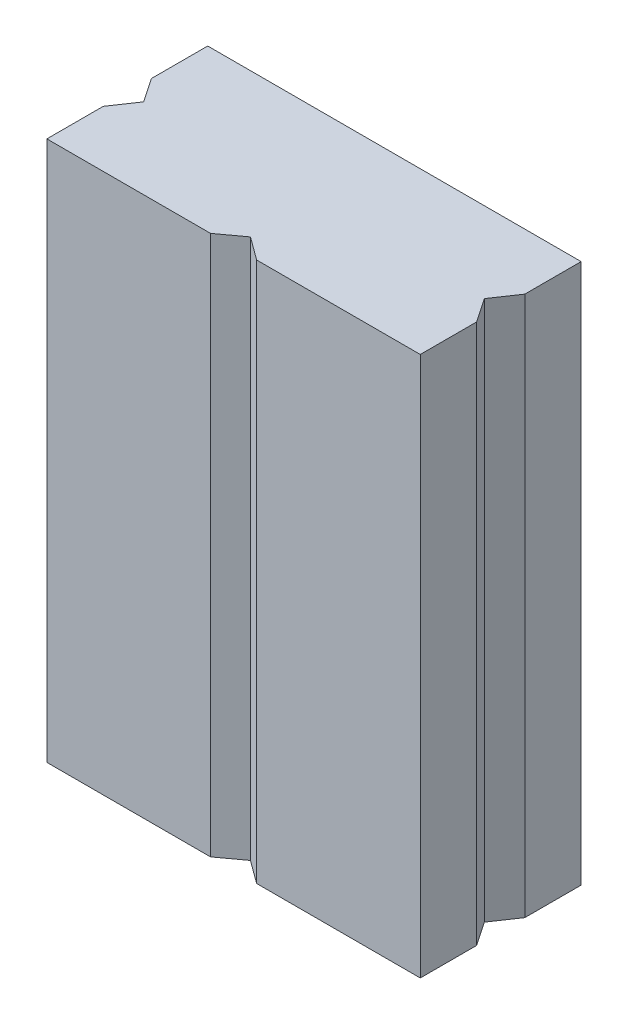
SolidWorks part; units mm, degrees
ref_plane "Front Plane" through (0, 0, 0) normal (0, 0, 1) x (1, 0, 0)
ref_plane "Top Plane" through (0, 0, 0) normal (0, 1, 0) x (1, 0, 0)
ref_plane "Right Plane" through (0, 0, 0) normal (1, 0, 0) x (0, 0, -1)
sketch "Sketch1" plane through (0, 0, 0) normal (0, 1, 0) x (1, 0, 0)
  line L0 (0, 0) -> (65, 0)
  line L1 (65, 0) -> (65, 28)
  line L2 (65, 28) -> (0, 28)
  line L3 (0, 28) -> (0, 0)
  line L4 (32.5, 0) -> (32.5, 2.939) construction
  line L5 (2.8366, 14) -> (0, 18.1942)
  line L6 (0, 14) -> (2.8366, 14) construction
  line L7 (2.8366, 14) -> (0, 9.8058)
  line L8 (62.1634, 14) -> (65, 18.1942)
  line L9 (62.1634, 14) -> (65, 9.8058)
  line L10 (32.5, 2.939) -> (28.4865, 0)
  line L11 (32.5, 2.939) -> (36.5135, 0)
  line L12 (0, 0) -> (32.5, 0) construction
  line L13 (2.8366, 14) -> (12.6976, 14) construction
  circle A0 centre (12.6976, 14) radius 2.4078
extrude "Boss-Extrude1" add sketch "Sketch1" along normal blind 94 contours L10 L11 L0 L1 L9 L8 L2 L3 L5 L7 | A0 region at (32.7042, 0, -14.087) region at (12.6976, 0, -14)
extrude "Cut-Extrude1" cut sketch "Sketch1<3>" along normal blind 5 contours A0 region at (12.6976, 0, -14)
sketch "Sketch1<3>" plane through (0, 0, 0) normal (0, 1, 0) x (1, 0, 0) same geometry as "Sketch1"
